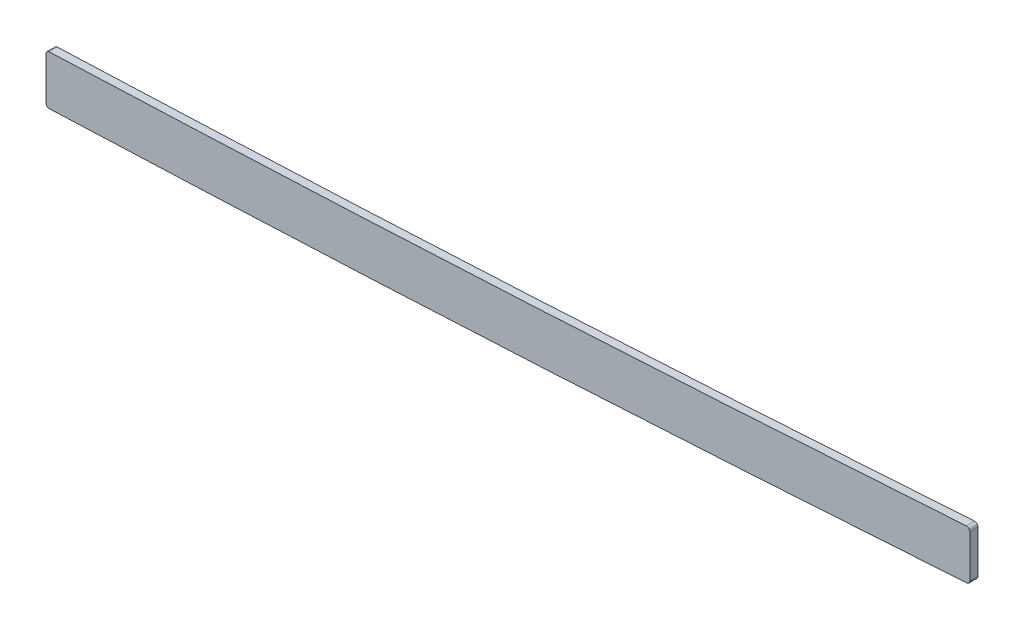
SolidWorks part; units mm, degrees
ref_plane "Front Plane" through (0, 0, 0) normal (0, 0, 1) x (1, 0, 0)
ref_plane "Top Plane" through (0, 0, 0) normal (0, 1, 0) x (1, 0, 0)
ref_plane "Right Plane" through (0, 0, 0) normal (1, 0, 0) x (0, 0, -1)
sketch "Sketch1" plane through (0, 0, 0) normal (0, 0, 1) x (1, 0, 0)
  line L0 (1046.2855, 53.4707) -> (499.61, 53.4707) construction
  line L1 (55, 0) -> (-55, 0) construction
  line L2 (1046.2855, -53.4707) -> (499.61, -53.4707)
  line L3 (1046.2855, -34.4207) -> (499.61, -34.4207)
  line L4 (99.06, -18.1493) -> (99.06, -37.7415)
  line L5 (2669.54, 9.5231) -> (2669.54, -9.569)
  line L6 (2311.4, -9.2457) -> (2311.4, -28.3104)
  spline S0 degree 5 poles (2699.7923, 7.5245) (2639.6368, 11.6572) (2579.4813, 15.4358) (2518.4981, 19.1485) (2436.3555, 23.2524) (2354.213, 26.6315) (2332.5703, 27.481) (2156.2686, 34.3778) (1979.9669, 41.6286) (1824.1143, 52.7713) (1636.9286, 53.5796) (1449.7429, 53.454) (1418.0067, 53.4707) (1324.8993, 53.4707) (1231.7919, 53.4707) (1170.4413, 53.4707) (1108.7841, 53.4707) (1047.1269, 53.4707) (1046.8464, 53.4707) (1046.5659, 53.4707) (1046.2855, 53.4707) knots 100.654805 100.654805 100.654805 100.654805 100.654805 100.654805 130.927897 130.927897 130.927897 141.337055 141.337055 141.337055 218.101815 218.101815 218.101815 233.772059 233.772059 233.772059 264.077723 264.077723 264.077723 264.216209 264.216209 264.216209 264.216209 264.216209 264.216209 weights 1 1 1 1 1 1 1 1 1 1 1 1 1 1 1 1 1 1 1 1 1 construction
  spline S1 degree 5 poles (499.61, 53.4707) (492.1368, 53.4707) (484.7543, 53.4707) (477.443, 53.4707) (448.5166, 53.4707) (419.5901, 53.4707) (398.3681, 53.4707) (355.6475, 53.4707) (312.927, 53.4707) (289.2351, 53.4703) (265.365, 53.4707) (241.4948, 53.4707) (241.4716, 53.4707) (241.4484, 53.4707) (241.4251, 53.4707) knots 19.90683 19.90683 19.90683 19.90683 19.90683 19.90683 23.637897 23.637897 23.637897 34.276546 34.276546 34.276546 46.401341 46.401341 46.401341 46.413154 46.413154 46.413154 46.413154 46.413154 46.413154 weights 1 1 1 1 1 1 1 1 1 1 1 1 1 1 1 construction
  spline S2 degree 5 poles (241.4251, 53.4707) (224.2869, 53.4707) (207.1495, 53.4673) (190.2039, 52.6866) (151.6561, 49.0319) (113.1083, 41.5037) (91.9499, 36.3426) (71.313, 30.9696) (50.6762, 24.7565) knots 0 0 0 0 0 0 8.713816 8.713816 8.713816 19.90683 19.90683 19.90683 19.90683 19.90683 19.90683 weights 1 1 1 1 1 1 1 1 1 construction
  spline S3 degree 5 poles (241.4251, -53.4707) (224.2869, -53.4707) (207.1495, -53.4673) (190.2039, -52.6866) (151.6561, -49.0319) (113.1083, -41.5037) (91.9499, -36.3426) (71.313, -30.9696) (50.6762, -24.7565) knots 0 0 0 0 0 0 8.713816 8.713816 8.713816 19.90683 19.90683 19.90683 19.90683 19.90683 19.90683 weights 1 1 1 1 1 1 1 1 1
  spline S4 degree 5 poles (499.61, -53.4707) (492.1368, -53.4707) (484.7543, -53.4707) (477.443, -53.4707) (448.5166, -53.4707) (419.5901, -53.4707) (398.3681, -53.4707) (355.6475, -53.4707) (312.927, -53.4707) (289.2351, -53.4703) (265.365, -53.4707) (241.4948, -53.4707) (241.4716, -53.4707) (241.4484, -53.4707) (241.4251, -53.4707) knots 19.90683 19.90683 19.90683 19.90683 19.90683 19.90683 23.637897 23.637897 23.637897 34.276546 34.276546 34.276546 46.401341 46.401341 46.401341 46.413154 46.413154 46.413154 46.413154 46.413154 46.413154 weights 1 1 1 1 1 1 1 1 1 1 1 1 1 1 1
  spline S5 degree 5 poles (2699.7923, -7.5245) (2639.6368, -11.6572) (2579.4813, -15.4358) (2518.4981, -19.1485) (2436.3555, -23.2524) (2354.213, -26.6315) (2332.5703, -27.481) (2156.2686, -34.3778) (1979.9669, -41.6286) (1824.1143, -52.7713) (1636.9286, -53.5796) (1449.7429, -53.454) (1418.0067, -53.4707) (1324.8993, -53.4707) (1231.7919, -53.4707) (1170.4413, -53.4707) (1108.7841, -53.4707) (1047.1269, -53.4707) (1046.8464, -53.4707) (1046.5659, -53.4707) (1046.2855, -53.4707) knots 100.654805 100.654805 100.654805 100.654805 100.654805 100.654805 130.927897 130.927897 130.927897 141.337055 141.337055 141.337055 218.101815 218.101815 218.101815 233.772059 233.772059 233.772059 264.077723 264.077723 264.077723 264.216209 264.216209 264.216209 264.216209 264.216209 264.216209 weights 1 1 1 1 1 1 1 1 1 1 1 1 1 1 1 1 1 1 1 1 1
  spline S6 degree 1 poles (2698.4867, 11.4807) (1046.2855, -34.4207) knots 0 0 1 1 construction
  spline S7 degree 1 poles (499.61, -34.4207) (241.4252, -34.4207) knots 0 0 1 1 construction
  spline S8 degree 1 poles (241.4252, -34.4207) (56.168, -6.5153) knots 0 0 1 1 construction
  spline S9 degree 3 poles (2698.4867, 11.4807) (2691.2474, 10.9833) (2679.1952, 10.1655) (2662.2765, 9.0388) (2635.6663, 7.2925) (2596.8577, 4.8261) (2545.7297, 1.7583) (2494.4053, -1.0986) (2451.533, -3.2666) (2417.1983, -4.8671) (2391.4571, -6.0036) (2365.6347, -7.0869) (2341.0156, -8.0785) (2320.7508, -8.8784) (2303.4475, -9.5581) (2284.7601, -10.2922) (2261.7633, -11.201) (2227.2853, -12.5838) (2184.1756, -14.3661) (2132.4291, -16.6074) (2063.4255, -19.7089) (1977.1749, -23.7005) (1873.7325, -28.1494) (1770.3746, -31.6575) (1667.0857, -33.7931) (1581.0111, -34.3832) (1512.074, -34.4278) (1443.0615, -34.4095) (1356.8009, -34.4244) (1218.7946, -34.4185) (1115.289, -34.4207) (1046.2855, -34.4207) knots 100.654805 100.654805 100.654805 100.654805 102.842388 104.300777 105.766098 110.877392 115.988686 121.09998 126.211274 128.766921 131.322568 133.878215 136.433862 138.55769 139.835514 141.545156 144.100803 146.656449 151.767743 156.879037 161.990331 172.212919 182.435507 192.658094 202.880682 213.10327 218.214564 223.325858 233.548445 243.771033 264.216209 264.216209 264.216209 264.216209
  spline S10 degree 3 poles (499.61, -34.4207) (488.6147, -34.4207) (472.2364, -34.4207) (449.9402, -34.4207) (427.7713, -34.4207) (405.8747, -34.4207) (384.5849, -34.4207) (368.9002, -34.4207) (353.3766, -34.4207) (332.6085, -34.4207) (306.2878, -34.4206) (274.0235, -34.4205) (252.271, -34.4207) (241.4252, -34.4207) knots 19.90683 19.90683 19.90683 19.90683 23.22012 24.876765 26.533411 29.846701 31.503346 33.159992 34.816637 36.473282 39.786573 43.099863 46.413154 46.413154 46.413154 46.413154
  spline S11 degree 3 poles (241.4252, -34.4207) (239.3949, -34.4207) (235.3223, -34.4205) (227.2744, -34.3987) (217.3194, -34.2975) (205.5307, -33.9764) (189.9633, -33.2126) (170.697, -31.5435) (147.5333, -28.3144) (125.4828, -24.2021) (107.4399, -20.1965) (92.2061, -16.4882) (75.9505, -12.2555) (63.6202, -8.7589) (56.168, -6.5153) knots 0 0 0 0 0.622088 1.244177 2.488354 3.732531 4.976707 7.465061 9.953415 12.441768 14.558235 15.802412 17.418476 19.90683 19.90683 19.90683 19.90683
  point P2 (0, 0)
  dimension "D1" = 50.6762
  dimension "D3" = 99.06
  dimension "D4" = 2669.54
  dimension "D5" = 2311.4
  dimension "D2" = 19.05
extrude "Boss-Extrude1" add sketch "Sketch1" along normal mid plane 3.175 contours L5 S9 L6 S5 region at (2490.5174, -10.3074, 0)
fillet "Fillet1" radius 1.27 4 edges at (2669.54, 9.5231, 0) (2311.4, -9.2457, 0)
